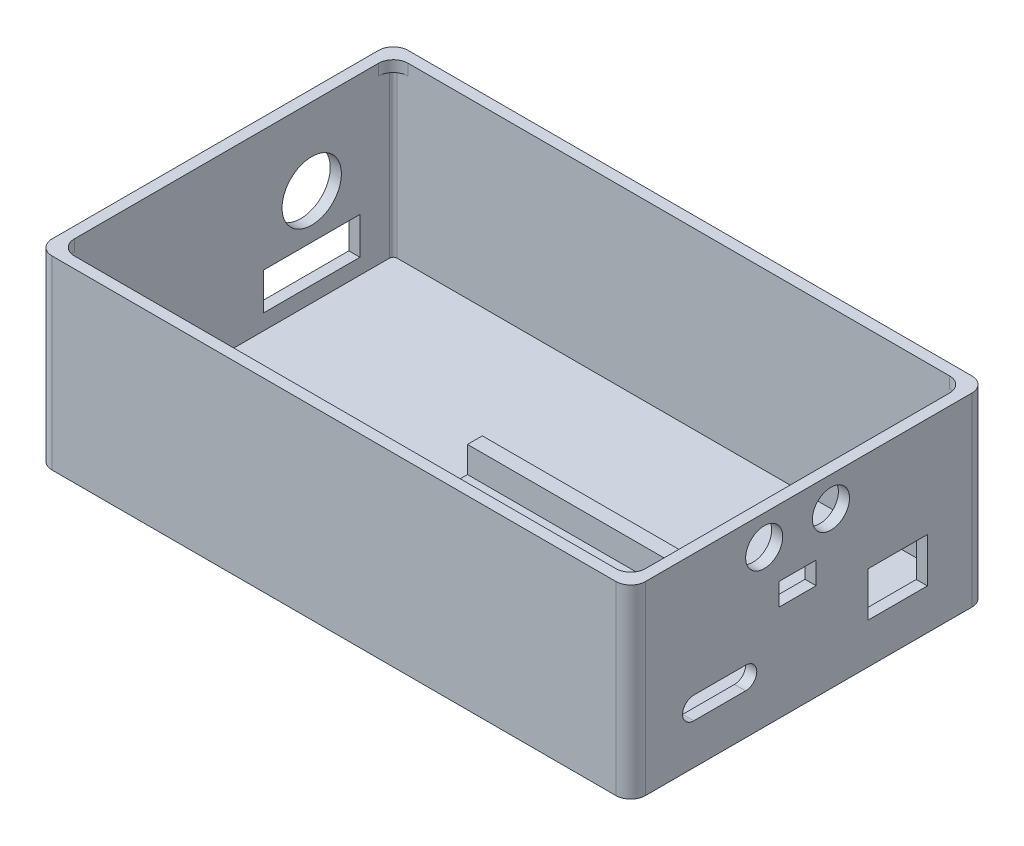
SolidWorks part; units mm, degrees
ref_plane "Спереди" through (0, 0, 0) normal (0, 0, 1) x (1, 0, 0)
ref_plane "Сверху" through (0, 0, 0) normal (0, 1, 0) x (1, 0, 0)
ref_plane "Справа" through (0, 0, 0) normal (1, 0, 0) x (0, 0, -1)
sketch "Эскиз3" plane through (0, 0, 0) normal (0, 1, 0) x (1, 0, 0)
  line L1 (-40, 24) -> (40, 24)
  line L2 (-40, 24) -> (-40, -24)
  line L3 (-40, -24) -> (40, -24)
  line L4 (40, 24) -> (40, -24)
  dimension "D1" = 24
  dimension "D2" = 24
  dimension "D3" = 40
  dimension "D4" = 40
extrude "Бобышка-Вытянуть1" add sketch "Эскиз3" along normal blind 25
fillet "Скругление1" radius 2 4 edges at (40, 12.5, -24) (40, 12.5, 24) (-40, 12.5, 24) (-40, 12.5, -24)
shell "Оболочка1" thickness 1.5
sketch "Эскиз5" plane through (0, 0, 0) normal (0, 1, 0) x (1, 0, 0)
  line L0 (40, 1) -> (-5, 1)
  line L2 (40, -22) -> (40, 22) construction
  line L3 (38, 24) -> (-38, 24) construction
  line L4 (40, -1) -> (-5, -1)
  line L5 (-5, -1) -> (-5, 1)
  line L8 (40, -1) -> (40, 1)
  dimension "D1" = 23
  dimension "D2" = 45
  dimension "D3" = 2
extrude "Бобышка-Вытянуть2" add sketch "Эскиз5" along normal blind 8
sketch "Эскиз7" plane through (0, 0, 0) normal (0, 1, 0) x (1, 0, 0)
  line L4 (40, -1) -> (-5, -1)
  line L7 (40, -22) -> (40, -1)
  line L9 (-5, -1) -> (-5, -24)
  line L10 (-38, -24) -> (38, -24) construction
  line L11 (38, -24) -> (-5, -24)
  arc A0 (38, -24) -> (40, -22) centre (38, -22) ccw construction
  arc A1 (38, -24) -> (40, -22) centre (38, -22) ccw
  dimension "D1" = 23
  dimension "D2" = 45
extrude "Бобышка-Вытянуть3" add sketch "Эскиз7" along normal blind 4.48
sketch "Эскиз8" plane through (40, 0, 0) normal (1, 0, 0) x (0, 0, -1)
  line L0 (-22, 5.48) -> (-17, 5.48)
  line L1 (-22, 25) -> (-22, 0) construction
  line L2 (22, 0) -> (22, 25) construction
  line L3 (-22, 0) -> (22, 0) construction
  line L4 (16, 5.48) -> (16, 26.3903) construction
  line L5 (16, 11.48) -> (16, 5.48)
  line L6 (16, 11.48) -> (8, 11.48)
  line L7 (8, 11.48) -> (8, 5.48)
  line L8 (8, 5.48) -> (16, 5.48)
  line L9 (-17, 29.385) -> (-17, -12.7109) construction
  line L10 (24, 25) -> (24, 0) construction
  line L11 (-24, 0) -> (-24, 25) construction
  line L12 (-15.5, 8.48) -> (-8.5, 8.48)
  line L14 (-8.5, 5.48) -> (-15.5, 5.48)
  line L15 (-17, 5.48) -> (-17, 6.98)
  line L16 (-15.5, 5.48) -> (22, 5.48)
  arc A0 (-15.5, 8.48) -> (-17, 6.98) centre (-15.5, 6.98) ccw
  arc A2 (-17, 6.98) -> (-15.5, 5.48) centre (-15.5, 6.98) ccw
  arc A3 (-8.5, 8.48) -> (-7, 6.98) centre (-8.5, 6.98) cw
  arc A4 (-7, 6.98) -> (-8.5, 5.48) centre (-8.5, 6.98) cw
  point P25 (-15.5, 8.48)
  point P27 (-7, 6.98)
  point P28 (-15.5, 5.48)
  point P29 (-8.5, 5.48)
  dimension "D1" = 5.48
  dimension "D2" = 8
  dimension "D3" = 8
  dimension "D4" = 6
  dimension "D5" = 7
  dimension "D6" = 7
  dimension "D7" = 3
  dimension "D8" = 1.5
  dimension "D9" = 15
  dimension "D10" = 1.5
  dimension "D11" = 3
  dimension "D12" = 3
  dimension "D13" = 1.5
extrude "Вырез-Вытянуть2" cut sketch "Эскиз8" against normal blind 4.03 contours L6 L7 L0 L5 region at (40, 8.48, -12)
extrude "Вырез-Вытянуть3" cut sketch "Эскиз8<4>" against normal blind 4.03 contours A4 A3 L12 A0 A2 L14 region at (40, 6.98, 12)
sketch "Эскиз8<4>" plane through (40, 0, 0) normal (1, 0, 0) x (0, 0, -1) same geometry as "Эскиз8"
sketch "Эскиз11" plane through (-40, 0, 0) normal (-1, 0, 0) x (0, 0, 1)
  line L0 (-18, 37.6806) -> (-18, -6.0464) construction
  line L1 (-24, 0) -> (-24, 25) construction
  line L4 (-18, 3.6) -> (-5, 3.6)
  line L5 (-22, 0) -> (22, 0) construction
  line L6 (-18, 3.6) -> (-18, 8.6)
  line L7 (-5, 3.6) -> (-5, 8.6)
  line L8 (-5, 8.6) -> (-18, 8.6)
  dimension "D1" = 6
  dimension "D2" = 3.6
  dimension "D3" = 13
  dimension "D4" = 5
extrude "Вырез-Вытянуть4" cut sketch "Эскиз11" against normal blind 4.03
sketch "Эскиз12" plane through (40, 0, 0) normal (1, 0, 0) x (0, 0, -1)
  line L0 (-22, 0) -> (22, 0) construction
  line L1 (-4, 16) -> (1, 16)
  line L2 (-4, 16) -> (-4, 13)
  line L3 (-4, 13) -> (1, 13)
  line L4 (1, 16) -> (1, 13)
  line L5 (8, 11.48) -> (8, 5.48) construction
  dimension "D1" = 5
  dimension "D2" = 3
  dimension "D3" = 13
  dimension "D4" = 7
extrude "Вырез-Вытянуть5" cut sketch "Эскиз12" against normal blind 4.03
sketch "Эскиз13" plane through (40, 0, 0) normal (1, 0, 0) x (0, 0, -1)
  line L0 (1, 16) -> (-4, 16) construction
  line L1 (1, 13) -> (1, 16) construction
  line L2 (-4, 16) -> (-4, 13) construction
  circle A0 centre (3, 21) radius 2.5
  circle A1 centre (-6, 21) radius 2.5
  dimension "D3" = 5
  dimension "D4" = 5
  dimension "D1" = 5
  dimension "D2" = 5
  dimension "D5" = 2
  dimension "D6" = 2
extrude "Вырез-Вытянуть6" cut sketch "Эскиз13" against normal blind 4.03
sketch "Эскиз14" plane through (-40, 0, 0) normal (-1, 0, 0) x (0, 0, 1)
  line L1 (-5, 8.6) -> (-18, 8.6) construction
  line L2 (-24, 0) -> (-24, 25) construction
  circle A0 centre (-11.5, 14.6) radius 4
  dimension "D1" = 8
  dimension "D2" = 6
  dimension "D3" = 12.5
extrude "Вырез-Вытянуть7" cut sketch "Эскиз14" against normal blind 4.03
sketch "Эскиз15" plane through (0, 25, 0) normal (0, 1, 0) x (1, 0, 0)
  line L4 (40, -22) -> (40, 22)
  line L5 (38, 24) -> (-38, 24)
  line L6 (-40, 22) -> (-40, -22)
  line L7 (-38, -24) -> (38, -24)
  line L8 (40, -22) -> (40, 22)
  line L9 (38, 24) -> (-38, 24)
  line L10 (-40, 22) -> (-40, -22)
  line L11 (-38, -24) -> (38, -24)
  line L12 (38.5, -20.5) -> (38.5, 20.5)
  line L13 (36.5, 22.5) -> (-36.5, 22.5)
  line L14 (-38.5, 20.5) -> (-38.5, -20.5)
  line L15 (-36.5, -22.5) -> (36.5, -22.5)
  line L16 (38, 24) -> (-38, 24) construction
  arc A0 (36.5, 22.5) -> (38.5, 20.5) centre (36.5, 20.5) cw
  arc A1 (36.5, -22.5) -> (38.5, -20.5) centre (36.5, -20.5) ccw
  arc A2 (-38.5, -20.5) -> (-36.5, -22.5) centre (-36.5, -20.5) ccw
  arc A3 (-38.5, 20.5) -> (-36.5, 22.5) centre (-36.5, 20.5) cw
  arc A4 (40, 22) -> (38, 24) centre (38, 22) ccw
  arc A5 (-38, 24) -> (-40, 22) centre (-38, 22) ccw
  arc A6 (-40, -22) -> (-38, -24) centre (-38, -22) ccw
  arc A7 (38, -24) -> (40, -22) centre (38, -22) ccw
  arc A8 (40, 22) -> (38, 24) centre (38, 22) ccw
  arc A9 (-38, 24) -> (-40, 22) centre (-38, 22) ccw
  arc A10 (-40, -22) -> (-38, -24) centre (-38, -22) ccw
  arc A11 (38, -24) -> (40, -22) centre (38, -22) ccw
  dimension "D6" = 2
  dimension "D7" = 2
  dimension "D8" = 2
  dimension "D9" = 2
  dimension "D2" = 1.5
  dimension "D3" = 1.5
  dimension "D4" = 1.5
  dimension "D5" = 1.5
  dimension "D1" = 0
extrude "Вырез-Вытянуть12" cut sketch "Эскиз15" against normal blind 4.03 contours L15 A1 L12 A0 L13 A3 L14 A2
sketch "Эскиз16" plane through (-40, 0, 0) normal (-1, 0, 0) x (0, 0, 1)
  line L0 (24, 25) -> (24, 0) construction
  line L1 (8, 10.48) -> (18, 10.48)
  line L2 (8, 10.48) -> (8, 5.48)
  line L3 (8, 5.48) -> (18, 5.48)
  line L4 (18, 10.48) -> (18, 5.48)
  line L5 (-22, 0) -> (22, 0) construction
  dimension "D1" = 10
  dimension "D2" = 5
  dimension "D3" = 6
  dimension "D4" = 5.48
extrude "Вырез-Вытянуть13" cut sketch "Эскиз16" against normal blind 4.03
sketch "Эскиз17" plane through (0, 0, 0) normal (0, 1, 0) x (1, 0, 0)
  line L0 (-40, 22) -> (-40, -22) construction
  line L1 (38, 24) -> (-38, 24) construction
  line L2 (40, -22) -> (40, 22) construction
  line L3 (-38, -24) -> (38, -24) construction
  line L4 (-40, 22) -> (-40, -22)
  line L5 (38, 24) -> (-38, 24)
  line L6 (40, -22) -> (40, 22)
  line L7 (-38, -24) -> (38, -24)
  arc A0 (-40, -22) -> (-38, -24) centre (-38, -22) ccw construction
  arc A1 (-38, 24) -> (-40, 22) centre (-38, 22) ccw construction
  arc A2 (40, 22) -> (38, 24) centre (38, 22) ccw construction
  arc A3 (38, -24) -> (40, -22) centre (38, -22) ccw construction
  arc A4 (-40, -22) -> (-38, -24) centre (-38, -22) ccw
  arc A5 (-38, 24) -> (-40, 22) centre (-38, 22) ccw
  arc A6 (40, 22) -> (38, 24) centre (38, 22) ccw
  arc A7 (38, -24) -> (40, -22) centre (38, -22) ccw
